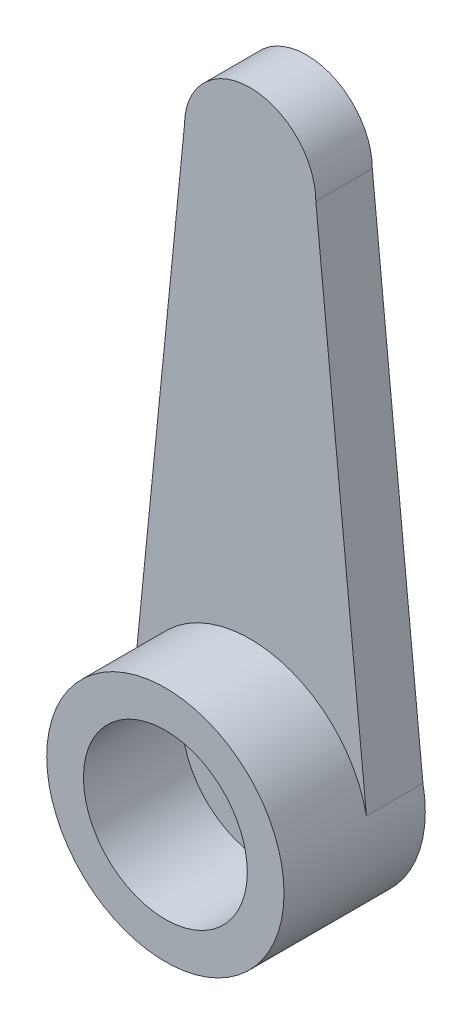
SolidWorks part; units mm, degrees
ref_plane "Front Plane" through (0, 0, 0) normal (0, 0, 1) x (1, 0, 0)
ref_plane "Top Plane" through (0, 0, 0) normal (0, 1, 0) x (1, 0, 0)
ref_plane "Right Plane" through (0, 0, 0) normal (1, 0, 0) x (0, 0, -1)
sketch "Sketch1" plane through (0, 0, 0) normal (0, 0, 1) x (1, 0, 0)
  line L0 (0, 0) -> (0, 21.1) construction
  line L1 (2.325, 18.775) -> (4.1171, 0.8306)
  line L2 (-2.325, 18.775) -> (-4.1171, 0.8306)
  circle A0 centre (0, 0) radius 4.2
  circle A1 centre (0, 0) radius 2.9
  circle A2 centre (0, 0) radius 1.5
  arc A3 (2.325, 18.775) -> (-2.325, 18.775) centre (0, 18.775) ccw
  dimension "D1" = 8.4
  dimension "D2" = 5.8
  dimension "D3" = 3
  dimension "D5" = 4.65
  dimension "D4" = 21.1
extrude "Boss-Extrude1" add sketch "Sketch1" along normal blind 2 contours A0 L0 A3 L2 | L0 A0 L1 A3 region at (-1.5915, 11.2116, 0) region at (1.5915, 11.2116, 0)
extrude "Boss-Extrude2" add sketch "Sketch1<3>" along normal blind 5 contours A1 A0 L2 L1 region at (4.061, 0.4056, 0)
sketch "Sketch1<3>" plane through (0, 0, 0) normal (0, 0, 1) x (1, 0, 0) same geometry as "Sketch1"
extrude "Boss-Extrude3" add sketch "Sketch1<4>" along normal blind 1.5 contours A2 A1 region at (-2.818, 0, 0)
sketch "Sketch1<4>" plane through (0, 0, 0) normal (0, 0, 1) x (1, 0, 0) same geometry as "Sketch1"
